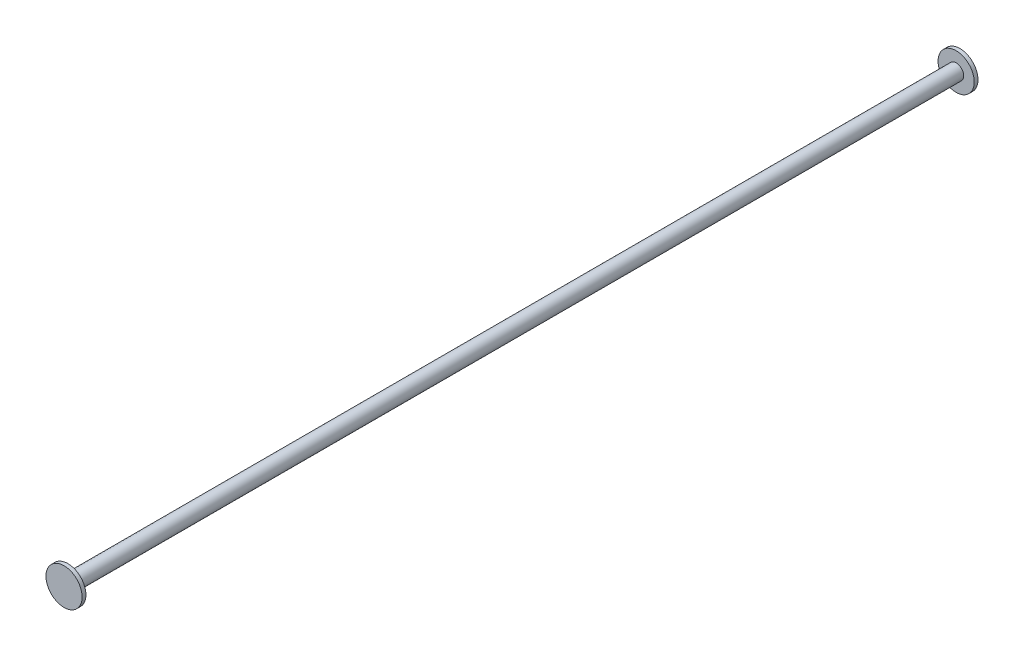
SolidWorks part; units mm, degrees
ref_plane "Front Plane" through (0, 0, 0) normal (0, 0, 1) x (1, 0, 0)
ref_plane "Top Plane" through (0, 0, 0) normal (0, 1, 0) x (1, 0, 0)
ref_plane "Right Plane" through (0, 0, 0) normal (1, 0, 0) x (0, 0, -1)
sketch "Sketch1" plane through (0, 0, 0) normal (0, 0, 1) x (1, 0, 0)
  line L5 (-1.4142, 1.4142) -> (1.4142, -1.4142) construction
  line L6 (-1.4142, -1.4142) -> (1.4142, 1.4142) construction
  circle A0 centre (0, 0) radius 2
  point P0 (0, 0)
  dimension "D3" = 4
extrude "Boss-Extrude1" add sketch "Sketch1" along normal mid plane 235
sketch "Sketch2" plane through (0, 0, 117.5) normal (0, 0, 1) x (1, 0, 0)
  circle A0 centre (0, 0) radius 4.7826
extrude "Boss-Extrude2" add sketch "Sketch2" along normal blind 1
mirror "Mirror2" about plane through (0, 0, 0) normal (0, 0, 1) of "Boss-Extrude2"
